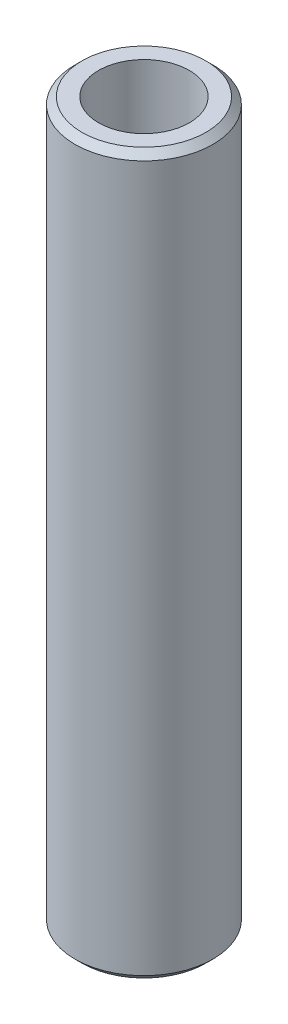
SolidWorks part; units mm, degrees
ref_plane "Front Plane" through (0, 0, 0) normal (0, 0, 1) x (1, 0, 0)
ref_plane "Top Plane" through (0, 0, 0) normal (0, 1, 0) x (1, 0, 0)
ref_plane "Right Plane" through (0, 0, 0) normal (1, 0, 0) x (0, 0, -1)
sketch "Sketch1" plane through (0, 0, 0) normal (0, 1, 0) x (1, 0, 0)
  circle A0 centre (0, 0) radius 57.5
  dimension "SHAFT_OD" = 115
extrude "Boss-Extrude1" add sketch "Sketch1" along normal blind 600
sketch "Sketch2" plane through (0, 0, 0) normal (0, 1, 0) x (1, 0, 0)
  circle A0 centre (0, 0) radius 37.8636
  dimension "BORE_D" = 75.7272
extrude "Cut-Extrude1" cut sketch "Sketch2" along normal through all
chamfer "Chamfer1" distance 5.8081 angle 45 2 edges at (0, 600, 57.5) (0, 0, 57.5)
